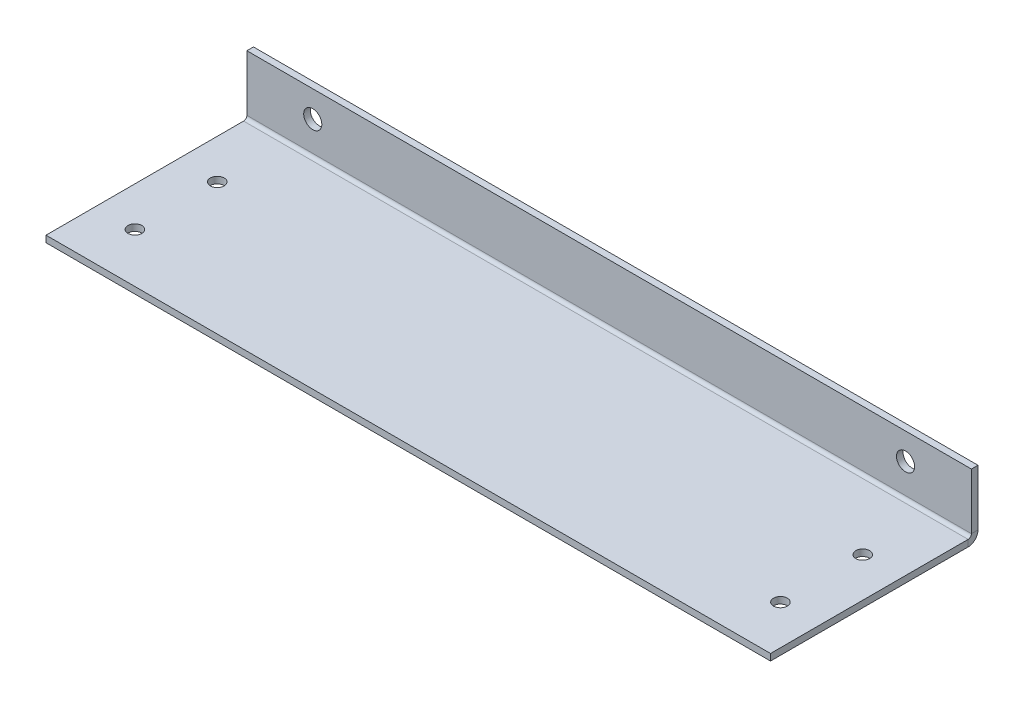
SolidWorks part; units mm, degrees
note: The reader was unsure of these and kept them because the rebuilt part matched: flange length of "边线-法兰1".
ref_plane "前视基准面" through (0, 0, 0) normal (0, 0, 1) x (1, 0, 0)
ref_plane "上视基准面" through (0, 0, 0) normal (0, 1, 0) x (1, 0, 0)
ref_plane "右视基准面" through (0, 0, 0) normal (1, 0, 0) x (0, 0, -1)
sketch "草图1" plane through (0, 0, 0) normal (0, 1, 0) x (1, 0, 0)
  line L1 (-110, 60) -> (110, 60)
  line L2 (-110, 60) -> (-110, 0)
  line L3 (-110, 0) -> (110, 0)
  line L4 (110, 60) -> (110, 0)
  point P5 (0, 0)
  dimension "D1" = 220
  dimension "D2" = 60
  dimension "D3" = 0
  dimension "D4" = 0
base flange "基体-法兰1" sketch "草图1" thickness 2 reverse thickness direction no parameters "D1"=1
edge flange "边线-法兰1" sketch "草图10" flange angle 90 flange length 20 flange position bend outside bend radius 1 thickness 2 relief rectangular parameters "D6"=10
bend "边线折弯1" bend radius 1 bend angle 90 parameters "D5"=1
sketch "草图10" plane through (0, 0, -60) normal (0, 0, -1) x (-1, 0, 0)
  line L0 (-110, 0) -> (110, 0) construction
  line L1 (-110, 0) -> (110, 0)
  line L2 (-110, 0) -> (-110, 18)
  line L3 (-110, 18) -> (110, 18)
  line L4 (110, 18) -> (110, 0)
hole_wizard "大小mm 暗销孔1" positions "3D草图1" profile "草图11" hole size "Ø8.0" standard "GB"
sketch3d "3D草图1"
  line L0 (110, 18, -61) -> (110, 1, -61) construction
  line L1 (-110, 18, -61) -> (110, 18, -61) construction
  line L2 (0, 18, -63) -> (0, -103.8247, -63) construction
  line L3 (-110, 18, -63) -> (110, 18, -63) construction
  line L5 (-110, 1, -61) -> (-110, 18, -61) construction
  point P0 (90, 10, -61)
  point P2 (-90, 10, -61)
  point P14 (0, 0, 0)
  point P15 (0, 0, 0)
  point P16 (0, 0, 0)
  dimension "D1" = 20
  dimension "D2" = 8
  dimension "D3" = 20
  dimension "D4" = 8
sketch "草图11" plane through (90, 10, -61) normal (1, 0, 0) x (0, -1, 0)
  line L0 (0, 0) -> (0, 9.6524)
  line L1 (0, 9.6524) -> (2.75, 8)
  line L2 (2.75, 8) -> (2.75, 0)
  line L5 (2.75, 0) -> (0, 0)
  line L10 (0, 9.6524) -> (-2.75, 8) construction
  line L11 (0, -6.35) -> (0, 107.95) construction
  dimension "孔直径" = 5.5
  dimension "孔深度" = 8
  dimension "导头角度" = 118
hole_wizard "M5 螺纹孔1" positions "3D草图2" profile "草图12" tap size "M5" standard "GB"
sketch3d "3D草图2"
  line L0 (110, 0, 0) -> (110, 0, -60) construction
  line L1 (-110, 0, 0) -> (110, 0, 0) construction
  line L2 (-110, 0, -60) -> (-110, 0, 0) construction
  point P0 (98, 0, -40)
  point P2 (98, 0, -15)
  point P4 (-98, 0, -40)
  point P6 (-98, 0, -15)
  dimension "D1" = 25
  dimension "D2" = 12
  dimension "D3" = 12
  dimension "D4" = 15
  dimension "D5" = 25
  dimension "D6" = 15
  dimension "D7" = 12
  dimension "D8" = 12
sketch "草图12" plane through (98, 0, -40) normal (1, 0, 0) x (0, 0, 1)
  line L0 (0, 0) -> (0, 13.6618)
  line L1 (0, 13.6618) -> (2.1, 12.4)
  line L2 (2.1, 12.4) -> (2.1, 0)
  line L5 (2.1, 0) -> (0, 0)
  line L10 (0, 13.6618) -> (-2.1, 12.4) construction
  line L11 (0, -6.35) -> (0, 107.95) construction
  dimension "螺纹孔钻头直径" = 4.2
  dimension "螺纹孔钻头深度" = 12.4
  dimension "导头角度" = 118
cosmetic thread "孔螺蚊线1"
cosmetic thread "孔螺蚊线2"
cosmetic thread "孔螺蚊线3"
cosmetic thread "孔螺蚊线4"
sketch "折弯-线1" plane through (0, 0, 0) normal (0, 1, 0) x (1, 0, 0)
sketch "边界框1" plane through (0, 0, 0) normal (0, 1, 0) x (1, 0, 0)
sheet metal parameters "钣金6" thickness 2 parameters "D1"=1
flat pattern "平板型式6" [suppressed]
sketch "折弯-线2" plane through (0, 0, 0) normal (0, 1, 0) x (1, 0, 0)
sketch "边界框2" [suppressed] plane through (0, 0, 0) normal (0, 1, 0) x (1, 0, 0)
sheet metal parameters "钣金7" thickness 2 parameters "D1"=1
flat pattern "平板型式6" [suppressed]
sketch "折弯-线2" plane through (0, 0, 0) normal (0, 1, 0) x (1, 0, 0)
sketch "边界框2" [suppressed] plane through (0, 0, 0) normal (0, 1, 0) x (1, 0, 0)
bend of the flat pattern "展平-<边线折弯1>1"
sheet metal parameters "钣金8" thickness 2 parameters "D1"=1
flat pattern "平板型式6" [suppressed]
sketch "折弯-线2" plane through (0, 0, 0) normal (0, 1, 0) x (1, 0, 0)
sketch "边界框2" [suppressed] plane through (0, 0, 0) normal (0, 1, 0) x (1, 0, 0)
bend of the flat pattern "展平-<边线折弯1>1"
sheet metal parameters "钣金9" thickness 2 parameters "D1"=1
flat pattern "平板型式6" [suppressed]
sketch "折弯-线2" plane through (0, 0, 0) normal (0, 1, 0) x (1, 0, 0)
sketch "边界框2" [suppressed] plane through (0, 0, 0) normal (0, 1, 0) x (1, 0, 0)
bend of the flat pattern "展平-<边线折弯1>1"
